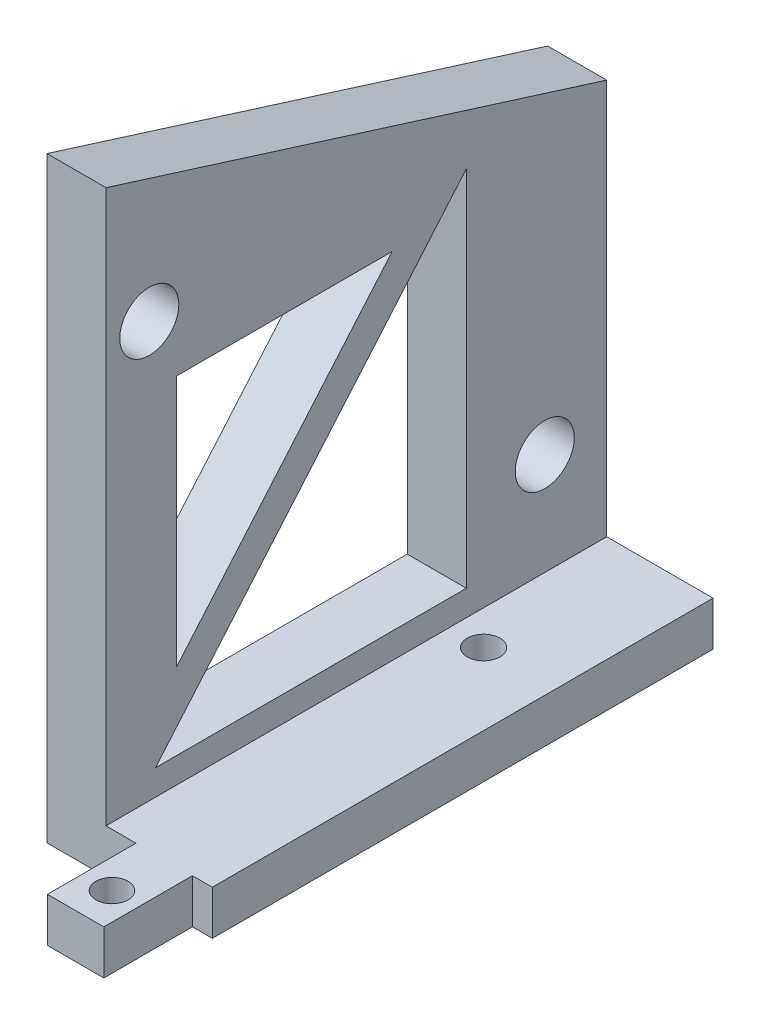
SolidWorks part; units mm, degrees
material "ABS"
ref_plane "Front Plane" through (0, 0, 0) normal (0, 0, 1) x (1, 0, 0)
ref_plane "Top Plane" through (0, 0, 0) normal (0, 1, 0) x (1, 0, 0)
ref_plane "Right Plane" through (0, 0, 0) normal (1, 0, 0) x (0, 0, -1)
sketch "Sketch2" plane through (0, 0, 0) normal (1, 0, 0) x (0, 0, -1)
  line L0 (-32.5747, 1.905) -> (-32.5747, 49.4466)
  line L1 (-32.5747, 1.905) -> (10.4974, 1.905)
  line L2 (-32.5747, 1.905) -> (-32.5747, -1.905)
  line L3 (-32.5747, -1.905) -> (10.4974, -1.905)
  line L4 (10.4974, 1.905) -> (10.4974, -1.905)
  line L6 (-1.5813, 35.3494) -> (-1.5813, 4.1082)
  line L7 (-32.5747, 49.4466) -> (10.4974, 35.9244)
  line L8 (10.4974, 35.9244) -> (10.4974, 1.905)
  line L9 (-1.5813, 4.1082) -> (-28.3177, 4.1082)
  line L10 (-28.3177, 4.1082) -> (-1.5813, 35.3494)
  line L11 (-26.5242, 32.382) -> (-26.5242, 10.6934)
  line L12 (-26.5242, 10.6934) -> (-7.9629, 32.382)
  line L13 (-7.9629, 32.382) -> (-26.5242, 32.382)
  circle A0 centre (5.1664, 10.6934) radius 2.54
  circle A1 centre (-28.8522, 37.6299) radius 2.54
  point P0 (0, 0)
  dimension "D2" = 5.08
  dimension "D1" = 3.81
  dimension "D3" = 43.3917
  dimension "D4" = 35.7249
  dimension "D5" = 8.7884
  dimension "D6" = 3.7225
extrude "Boss-Extrude1" add sketch "Sketch2" along normal blind 5.08 contours L8 L7 L0 L1 region at (0, 24.9605, 11.4161)
extrude "Boss-Extrude2" add sketch "Sketch2<3>" along normal blind 14.224 contours L4 L1 L2 L3 region at (0, 0, 11.0387)
sketch "Sketch2<3>" plane through (0, 0, 0) normal (1, 0, 0) x (0, 0, -1) same geometry as "Sketch2"
sketch "Sketch3" plane through (0, 1.905, 0) normal (0, 1, 0) x (1, 0, 0)
  circle A0 centre (8.0348, -3.0491) radius 1.4063
  point P3 (0, 0)
extrude "Cut-Extrude1" cut sketch "Sketch3" against normal through all
sketch "Sketch4" plane through (0, 0, 32.5747) normal (0, 0, 1) x (1, 0, 0)
  line L0 (7.6599, 1.905) -> (7.6599, -1.905)
  line L1 (14.224, 1.905) -> (5.08, 1.905) construction
  line L2 (7.6599, -1.905) -> (12.5094, -1.905)
  line L3 (12.5094, -1.905) -> (12.5094, 1.905)
  line L4 (12.5094, 1.905) -> (7.6599, 1.905)
  line L5 (14.224, -1.905) -> (0, -1.905) construction
extrude "Boss-Extrude3" add sketch "Sketch4" along normal blind 7.62
sketch "Sketch5" plane through (0, 1.905, 0) normal (0, 1, 0) x (1, 0, 0)
  circle A0 centre (10.1589, -37.143) radius 1.3877
  point P3 (0, 0)
extrude "Cut-Extrude2" cut sketch "Sketch5" against normal through all
